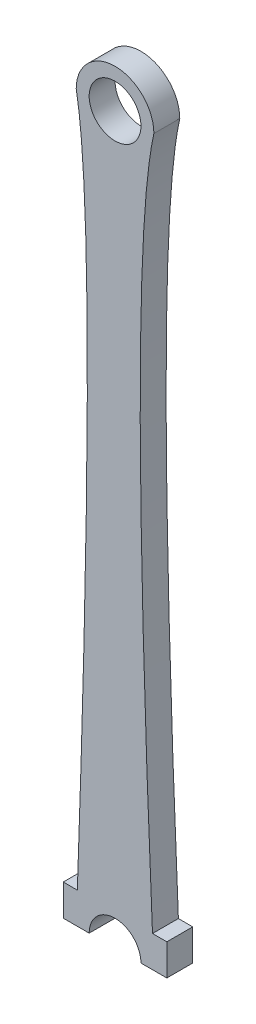
SolidWorks part; units mm, degrees
ref_plane "Front Plane" through (0, 0, 0) normal (0, 0, 1) x (1, 0, 0)
ref_plane "Top Plane" through (0, 0, 0) normal (0, 1, 0) x (1, 0, 0)
ref_plane "Right Plane" through (0, 0, 0) normal (1, 0, 0) x (0, 0, -1)
sketch "Sketch1" plane through (0, 0, 0) normal (0, 0, 1) x (1, 0, 0)
  line L0 (0, 204.7322) -> (0, -65.2678) construction
  line L1 (-15, -75.2678) -> (-10, -75.2678)
  line L2 (10, -75.2678) -> (15, -75.2678)
  line L3 (-15, -75.2678) -> (-20, -75.2678)
  line L4 (-20, -75.2678) -> (-20, -63.1536)
  line L5 (-20, -63.1536) -> (-14.5625, -63.1536)
  line L6 (15, -75.2678) -> (20, -75.2678)
  line L7 (20, -75.2678) -> (20, -63.1536)
  line L8 (20, -63.1536) -> (14.4593, -63.1536)
  arc A0 (10, -75.2678) -> (-10, -75.2678) centre (0, -75.2678) ccw
  circle A1 centre (0, 204.7322) radius 10
  arc A3 (15, 204.7322) -> (-15, 204.7322) centre (0, 204.7322) ccw
  spline S0 degree 3 poles (-15, 204.7322) (-9.4315, 174.7057) (-9.2857, 85.4104) (-14.5625, -63.1536) knots 0 0 0 0 0.973812 0.973812 0.973812 0.973812
  spline S1 degree 3 poles (15, 204.7322) (8.1343, 174.351) (7.9541, 85.0558) (14.4593, -63.1536) knots 0 0 0 0 0.973751 0.973751 0.973751 0.973751
extrude "Boss-Extrude1" add sketch "Sketch1" along normal blind 10
ref_axis "Axis1" through (0, -75.2678, 10) along (0, 0, -1)
ref_axis "Axis2" through (0, 204.7322, 10) along (0, 0, -1)
sketch "Sketch2" plane through (0, -75.2678, 0) normal (0, -1, 0) x (1, 0, 0)
  line L0 (15, 10) -> (15, 0) construction
  line L1 (10, 10) -> (20, 10) construction
  line L2 (10, 0) -> (20, 0) construction
sketch "Sketch3" plane through (0, -75.2678, 0) normal (0, -1, 0) x (1, 0, 0)
  line L3 (-10, 5) -> (-17, 5)
  line L6 (-10, 10) -> (-10, 0) construction
hole_wizard "Ø4.0 (4) Diameter Hole2" positions "Sketch6" profile "Sketch7" hole size "Ø4.0" standard "ANSI Metric"
sketch "Sketch6" plane through (0, -75.2678, 0) normal (0, -1, 0) x (-1, 0, 0)
  point P0 (17, -5)
sketch "Sketch7" plane through (-17, -75.2678, 5) normal (1, 0, 0) x (0, 0, -1)
  line L0 (0, 0) -> (0, 11.2017)
  line L1 (0, 11.2017) -> (2, 10)
  line L2 (2, 10) -> (2, 0)
  line L5 (2, 0) -> (0, 0)
  line L10 (0, 11.2017) -> (-2, 10) construction
  line L11 (0, -6.35) -> (0, 107.95) construction
  dimension "Hole Dia." = 4
  dimension "Hole Depth" = 10
  dimension "Drill Angle" = 118
mirror "Mirror2" about plane through (0, 0, 0) normal (1, 0, 0) of "Ø4.0 (4) Diameter Hole2"
